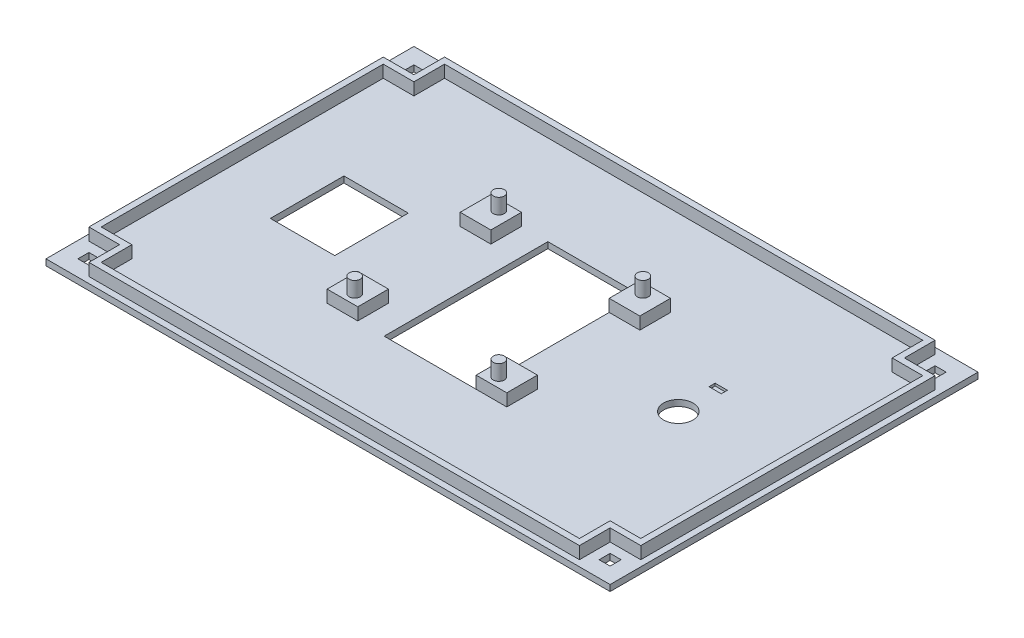
SolidWorks part; units mm, degrees
ref_plane "Спереди" through (0, 0, 0) normal (0, 0, 1) x (1, 0, 0)
ref_plane "Сверху" through (0, 0, 0) normal (0, 1, 0) x (1, 0, 0)
ref_plane "Справа" through (0, 0, 0) normal (1, 0, 0) x (0, 0, -1)
sketch "Эскиз1" plane through (0, 0, 0) normal (0, 1, 0) x (1, 0, 0)
  line L0 (0, 0) -> (92, 0)
  line L1 (0, 0) -> (0, 60)
  line L2 (0, 60) -> (92, 60)
  line L3 (92, 0) -> (92, 60)
  dimension "D1" = 60
  dimension "D2" = 92
extrude "Бобышка-Вытянуть1" add sketch "Эскиз1" along normal blind 1
sketch "Эскиз2" plane through (0, 1, 0) normal (0, 1, 0) x (1, 0, 0)
  line L0 (0, 60) -> (0, 0) construction
  line L1 (91, 1) -> (1, 1)
  line L2 (91, 1) -> (91, 59)
  line L3 (91, 59) -> (1, 59)
  line L4 (1, 1) -> (1, 59)
  line L5 (92, 60) -> (0, 60) construction
  line L6 (92, 0) -> (92, 60) construction
  line L7 (0, 0) -> (92, 0) construction
  line L8 (3.5, 4.4) -> (3.5, 2.6) construction
  line L9 (1, 59) -> (6, 59)
  line L10 (1, 59) -> (1, 54)
  line L11 (1, 54) -> (6, 54)
  line L12 (6, 59) -> (6, 54)
  line L13 (91, 59) -> (86, 59)
  line L14 (91, 59) -> (91, 54)
  line L15 (91, 54) -> (86, 54)
  line L16 (86, 59) -> (86, 54)
  line L17 (91, 1) -> (86, 1)
  line L18 (91, 1) -> (91, 6)
  line L19 (91, 6) -> (86, 6)
  line L20 (86, 1) -> (86, 6)
  line L21 (1, 1) -> (6, 1)
  line L22 (1, 1) -> (1, 6)
  line L23 (1, 6) -> (6, 6)
  line L24 (6, 1) -> (6, 6)
  line L25 (2.6, 57.4) -> (4.4, 57.4)
  line L26 (2.6, 57.4) -> (2.6, 55.6)
  line L27 (2.6, 55.6) -> (4.4, 55.6)
  line L28 (4.4, 57.4) -> (4.4, 55.6)
  line L29 (87.6, 57.4) -> (89.4, 57.4)
  line L30 (87.6, 57.4) -> (87.6, 55.6)
  line L31 (87.6, 55.6) -> (89.4, 55.6)
  line L32 (89.4, 57.4) -> (89.4, 55.6)
  line L33 (87.6, 4.4) -> (89.4, 4.4)
  line L34 (87.6, 4.4) -> (87.6, 2.6)
  line L35 (87.6, 2.6) -> (89.4, 2.6)
  line L36 (89.4, 4.4) -> (89.4, 2.6)
  line L37 (2.6, 4.4) -> (4.4, 4.4)
  line L38 (2.6, 4.4) -> (2.6, 2.6)
  line L39 (2.6, 2.6) -> (4.4, 2.6)
  line L40 (4.4, 4.4) -> (4.4, 2.6)
  line L41 (2.6, 3.5) -> (4.4, 3.5) construction
  line L42 (3.5, 57.4) -> (3.5, 55.6) construction
  line L43 (2.6, 56.5) -> (4.4, 56.5) construction
  line L44 (88.5, 57.4) -> (88.5, 55.6) construction
  line L45 (87.6, 56.5) -> (89.4, 56.5) construction
  line L46 (88.5, 4.4) -> (88.5, 2.6) construction
  line L47 (87.6, 3.5) -> (89.4, 3.5) construction
  line L48 (3.5, 54) -> (3.5, 59) construction
  line L49 (6, 56.5) -> (1, 56.5) construction
  line L50 (86, 56.5) -> (91, 56.5) construction
  line L51 (88.5, 54) -> (88.5, 59) construction
  line L52 (88.5, 6) -> (88.5, 1) construction
  line L53 (86, 3.5) -> (91, 3.5) construction
  line L54 (3.5, 6) -> (3.5, 1) construction
  line L55 (6, 3.5) -> (1, 3.5) construction
  dimension "D1" = 1
  dimension "D2" = 1
  dimension "D3" = 1
  dimension "D4" = 1
  dimension "D5" = 5
  dimension "D6" = 5
  dimension "D7" = 5
  dimension "D8" = 5
  dimension "D9" = 5
  dimension "D10" = 5
  dimension "D11" = 5
  dimension "D12" = 5
  dimension "D13" = 1.8
  dimension "D14" = 1.8
  dimension "D15" = 1.8
  dimension "D16" = 1.8
  dimension "D17" = 1.8
  dimension "D18" = 1.8
  dimension "D19" = 1.8
  dimension "D20" = 1.8
sketch "Эскиз3" plane through (0, 1, 0) normal (0, 1, 0) x (1, 0, 0)
  line L0 (7, 58) -> (7, 53)
  line L1 (7, 53) -> (2, 53)
  line L2 (2, 53) -> (2, 7)
  line L3 (2, 7) -> (7, 7)
  line L4 (7, 7) -> (7, 2)
  line L5 (7, 2) -> (85, 2)
  line L6 (85, 2) -> (85, 7)
  line L7 (85, 7) -> (90, 7)
  line L8 (90, 7) -> (90, 53)
  line L9 (90, 53) -> (85, 53)
  line L10 (85, 53) -> (85, 58)
  line L11 (85, 58) -> (7, 58)
  line L12 (6, 59) -> (6, 54) construction
  line L13 (91, 59) -> (1, 59) construction
  line L14 (1, 1) -> (1, 59) construction
  line L15 (1, 6) -> (6, 6) construction
  line L16 (91, 1) -> (1, 1) construction
  line L17 (86, 1) -> (86, 6) construction
  line L18 (91, 6) -> (86, 6) construction
  line L19 (91, 1) -> (91, 59) construction
  line L20 (91, 54) -> (86, 54) construction
  line L21 (86, 59) -> (86, 54) construction
  line L22 (86, 54) -> (91, 54)
  line L23 (91, 54) -> (91, 6)
  line L24 (91, 6) -> (86, 6)
  line L25 (86, 6) -> (86, 1)
  line L26 (86, 1) -> (6, 1)
  line L27 (6, 1) -> (6, 6)
  line L28 (6, 6) -> (1, 6)
  line L29 (1, 6) -> (1, 54)
  line L30 (1, 54) -> (6, 54)
  line L31 (6, 54) -> (6, 59)
  line L32 (6, 59) -> (86, 59)
  line L33 (86, 59) -> (86, 54)
  dimension "D1" = 1
  dimension "D2" = 1
  dimension "D3" = 1
  dimension "D4" = 1
  dimension "D5" = 1
  dimension "D6" = 1
  dimension "D7" = 1
  dimension "D8" = 1
  dimension "D9" = 1
  dimension "D10" = 1
  dimension "D11" = 1
  dimension "D12" = 1
extrude "Бобышка-Вытянуть3" add sketch "Эскиз3" along normal blind 2
sketch "Эскиз6" plane through (0, 1, 0) normal (0, 1, 0) x (1, 0, 0)
  line L1 (2.6, 57.4) -> (4.4, 57.4)
  line L2 (2.6, 57.4) -> (2.6, 55.6)
  line L3 (2.6, 55.6) -> (4.4, 55.6)
  line L4 (4.4, 57.4) -> (4.4, 55.6)
extrude "Вырез-Вытянуть3" cut sketch "Эскиз6" against normal blind 1
sketch "Эскиз7" plane through (0, 1, 0) normal (0, 1, 0) x (1, 0, 0)
  line L1 (87.6, 57.4) -> (89.4, 57.4)
  line L2 (87.6, 57.4) -> (87.6, 55.6)
  line L3 (87.6, 55.6) -> (89.4, 55.6)
  line L4 (89.4, 57.4) -> (89.4, 55.6)
extrude "Вырез-Вытянуть4" cut sketch "Эскиз7" against normal blind 1
sketch "Эскиз8" plane through (0, 1, 0) normal (0, 1, 0) x (1, 0, 0)
  line L1 (87.6, 4.4) -> (89.4, 4.4)
  line L2 (87.6, 4.4) -> (87.6, 2.6)
  line L3 (87.6, 2.6) -> (89.4, 2.6)
  line L4 (89.4, 4.4) -> (89.4, 2.6)
extrude "Вырез-Вытянуть5" cut sketch "Эскиз8" against normal blind 1
sketch "Эскиз9" plane through (0, 1, 0) normal (0, 1, 0) x (1, 0, 0)
  line L1 (2.6, 4.4) -> (4.4, 4.4)
  line L2 (2.6, 4.4) -> (2.6, 2.6)
  line L3 (2.6, 2.6) -> (4.4, 2.6)
  line L4 (4.4, 4.4) -> (4.4, 2.6)
extrude "Вырез-Вытянуть6" cut sketch "Эскиз9" against normal blind 1
sketch "Эскиз10" plane through (0, 1, 0) normal (0, 1, 0) x (1, 0, 0)
  line L0 (12.5878, 30) -> (23.0878, 30) construction
  line L1 (12.5878, 36) -> (23.0878, 36)
  line L2 (12.5878, 36) -> (12.5878, 24)
  line L3 (12.5878, 24) -> (23.0878, 24)
  line L4 (23.0878, 36) -> (23.0878, 24)
  line L5 (2, 30) -> (90, 30) construction
  line L6 (2, 53) -> (2, 7) construction
  line L7 (90, 7) -> (90, 53) construction
  dimension "D1" = 10.5
  dimension "D2" = 12
sketch "Эскиз11" plane through (0, 1, 0) normal (0, 1, 0) x (1, 0, 0)
  line L0 (73.1241, 37) -> (73.1241, 36) construction
  line L1 (72.1241, 37) -> (74.1241, 37)
  line L2 (72.1241, 37) -> (72.1241, 36)
  line L3 (72.1241, 36) -> (74.1241, 36)
  line L4 (74.1241, 37) -> (74.1241, 36)
  line L5 (70.7241, 30) -> (75.5241, 30) construction
  line L6 (2, 30) -> (90, 30) construction
  circle A0 centre (73.1241, 30) radius 2.4
  dimension "D1" = 4.8
  dimension "D2" = 1
  dimension "D3" = 2
  dimension "D4" = 6
sketch "Эскиз14" plane through (0, 1, 0) normal (0, 1, 0) x (1, 0, 0)
  line L0 (46, 58) -> (46, 2) construction
  line L1 (85, 58) -> (7, 58) construction
  line L2 (7, 2) -> (85, 2) construction
  line L3 (90, 7) -> (90, 53) construction
  line L4 (2, 30) -> (90, 30) construction
  line L5 (2, 53) -> (2, 7) construction
sketch "Эскиз15" plane through (0, 1, 0) normal (0, 1, 0) x (1, 0, 0)
  line L0 (2, 30) -> (90, 30) construction
  line L1 (38.5, 43.35) -> (53.5, 43.35)
  line L2 (38.5, 43.35) -> (38.5, 16.65)
  line L3 (38.5, 16.65) -> (53.5, 16.65)
  line L4 (53.5, 43.35) -> (53.5, 16.65)
  line L5 (38.5, 30) -> (53.5, 30) construction
  line L6 (46, 43.35) -> (46, 16.65) construction
  line L7 (46, 58) -> (46, 2) construction
  dimension "D1" = 15
  dimension "D2" = 26.7
extrude "Вырез-Вытянуть8" cut sketch "Эскиз15" against normal blind 1
sketch "Эскиз17" plane through (0, 1, 0) normal (0, 1, 0) x (1, 0, 0)
  line L1 (53.5, 43.35) -> (34.2, 43.35)
  line L2 (53.5, 43.35) -> (53.5, 16.65)
  line L3 (53.5, 16.65) -> (34.2, 16.65)
  line L4 (34.2, 43.35) -> (34.2, 16.65)
  dimension "D1" = 19.3
  dimension "D2" = 26.7
sketch "Эскиз18" plane through (0, 1, 0) normal (0, 1, 0) x (1, 0, 0)
  line L1 (34.2, 43.35) -> (29.2, 43.35)
  line L2 (34.2, 43.35) -> (34.2, 38.35)
  line L3 (34.2, 38.35) -> (29.2, 38.35)
  line L4 (29.2, 43.35) -> (29.2, 38.35)
  line L5 (34.2, 16.65) -> (29.2, 16.65)
  line L6 (34.2, 16.65) -> (34.2, 21.65)
  line L7 (34.2, 21.65) -> (29.2, 21.65)
  line L8 (29.2, 16.65) -> (29.2, 21.65)
  line L9 (53.5, 43.35) -> (58.5, 43.35)
  line L10 (53.5, 43.35) -> (53.5, 38.35)
  line L11 (53.5, 38.35) -> (58.5, 38.35)
  line L12 (58.5, 43.35) -> (58.5, 38.35)
  line L13 (53.5, 16.65) -> (58.5, 16.65)
  line L14 (53.5, 16.65) -> (53.5, 21.65)
  line L15 (53.5, 21.65) -> (58.5, 21.65)
  line L16 (58.5, 16.65) -> (58.5, 21.65)
  dimension "D1" = 5
  dimension "D2" = 5
extrude "Бобышка-Вытянуть4" add sketch "Эскиз18" along normal blind 2
sketch "Эскиз19" plane through (0, 3, 0) normal (0, 1, 0) x (1, 0, 0)
  line L0 (31.2, 18.25) -> (33, 18.25) construction
  line L1 (54.7, 18.25) -> (56.5, 18.25) construction
  line L2 (55.6, 19.15) -> (55.6, 17.35) construction
  line L3 (32.1, 19.15) -> (32.1, 17.35) construction
  line L4 (32.1, 42.65) -> (32.1, 40.85) construction
  line L5 (31.2, 41.75) -> (33, 41.75) construction
  line L6 (55.6, 42.65) -> (55.6, 40.85) construction
  line L7 (54.7, 41.75) -> (56.5, 41.75) construction
  line L8 (2, 30) -> (90, 30) construction
  line L9 (34.2, 38.35) -> (34.2, 43.35) construction
  circle A0 centre (32.1, 41.75) radius 0.9
  circle A1 centre (32.1, 18.25) radius 0.9
  circle A2 centre (55.6, 41.75) radius 0.9
  circle A3 centre (55.6, 18.25) radius 0.9
  dimension "D1" = 1.8
  dimension "D2" = 1.8
  dimension "D3" = 1.8
  dimension "D4" = 1.8
  dimension "D5" = 23.5
  dimension "D6" = 11.75
  dimension "D7" = 23.5
  dimension "D8" = 2.1
extrude "Бобышка-Вытянуть5" add sketch "Эскиз19" along normal blind 2.5
extrude "Вырез-Вытянуть9" cut sketch "Эскиз10" against normal blind 1
sketch "Эскиз20" plane through (0, 1, 0) normal (0, 1, 0) x (1, 0, 0)
  circle A0 centre (73.1241, 30) radius 2.4
extrude "Вырез-Вытянуть11" cut sketch "Эскиз20" against normal blind 1
sketch "Эскиз21" plane through (0, 1, 0) normal (0, 1, 0) x (1, 0, 0)
  line L1 (72.1241, 37) -> (74.1241, 37)
  line L2 (72.1241, 37) -> (72.1241, 36)
  line L3 (72.1241, 36) -> (74.1241, 36)
  line L4 (74.1241, 37) -> (74.1241, 36)
extrude "Вырез-Вытянуть12" cut sketch "Эскиз21" against normal blind 0.4
sketch "Эскиз22" plane through (0, 0, 0) normal (0, -1, 0) x (-1, 0, 0)
  text T0 "СТАРТ" font "Arial" height in points 12
  text T1 "без ALARM" font "Arial" height in points 12
  text T2 "c ALARM" font "Arial" height in points 12
  point P6 (-63.931, 21.2966)
  point P7 (-62.2386, 44.1757)
extrude "Вырез-Вытянуть13" cut sketch "Эскиз22" against normal blind 0.4
